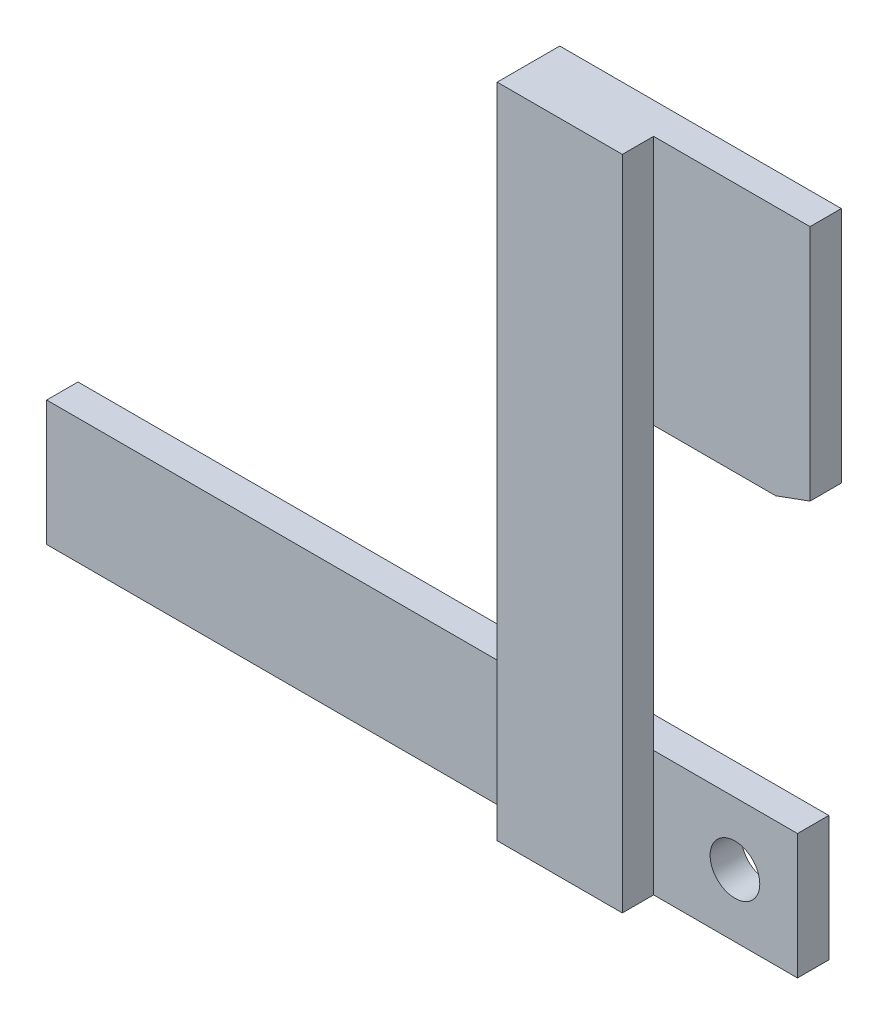
SolidWorks part; units mm, degrees
ref_plane "Front Plane" through (0, 0, 0) normal (0, 0, 1) x (1, 0, 0)
ref_plane "Top Plane" through (0, 0, 0) normal (0, 1, 0) x (1, 0, 0)
ref_plane "Right Plane" through (0, 0, 0) normal (1, 0, 0) x (0, 0, -1)
sketch "Sketch1" plane through (0, 0, 0) normal (0, 0, 1) x (1, 0, 0)
  line L1 (-76.2, -12.7) -> (76.2, -12.7)
  line L2 (-76.2, -12.7) -> (-76.2, 12.7)
  line L3 (-76.2, 12.7) -> (76.2, 12.7)
  line L4 (76.2, -12.7) -> (76.2, 12.7)
  line L5 (-76.2, -12.7) -> (76.2, 12.7) construction
  line L6 (-76.2, 12.7) -> (76.2, -12.7) construction
  point P0 (0, 0)
  dimension "D1" = 25.4
  dimension "D2" = 152.4
extrude "Extrude1" add sketch "Sketch1" along normal blind 6.35
sketch "Sketch2" plane through (0, 0, 6.35) normal (0, 0, 1) x (1, 0, 0)
  line L0 (-76.2, -12.7) -> (76.2, -12.7) construction
  line L1 (46.99, -12.7) -> (21.59, -12.7)
  line L2 (46.99, -12.7) -> (46.99, 120.65)
  line L3 (46.99, 120.65) -> (21.59, 120.65)
  line L4 (21.59, -12.7) -> (21.59, 120.65)
  line L5 (76.2, -12.7) -> (76.2, 12.7) construction
  dimension "D1" = 25.4
  dimension "D2" = 133.35
  dimension "D3" = 29.21
extrude "Extrude2" add sketch "Sketch2" along normal blind 6.35
sketch "Sketch3" plane through (0, 0, 6.35) normal (0, 0, -1) x (-1, 0, 0)
  line L0 (-46.99, 120.65) -> (-21.59, 120.65) construction
  line L1 (-21.59, 120.65) -> (-78.74, 120.65)
  line L2 (-21.59, 120.65) -> (-21.59, 69.85)
  line L3 (-21.59, 69.85) -> (-78.74, 69.85)
  line L4 (-78.74, 120.65) -> (-78.74, 69.85)
  line L6 (-21.59, 120.65) -> (-21.59, 12.7) construction
  dimension "D1" = 50.8
  dimension "D2" = 57.15
extrude "Extrude3" add sketch "Sketch3" along normal blind 6.35
chamfer "Chamfer1" distance 2.54 angle 70 1 edges at (78.74, 69.85, 3.175) first distance on face at (78.74, 95.25, 3.175)
sketch "Sketch4" plane through (0, 0, 6.35) normal (0, 0, 1) x (1, 0, 0)
  line L0 (76.2, 0) -> (63.5, 0) construction
  line L1 (76.2, -12.7) -> (76.2, 12.7) construction
  dimension "D1" = 12.7
hole_wizard "3/8 Clearance Hole1" positions "3DSketch1" profile "Sketch5" hole size "3/8" standard "Ansi Inch"
sketch3d "3DSketch1"
  point P0 (63.5, 0, 6.35)
sketch "Sketch5" plane through (63.5, 0, 6.35) normal (1, 0, 0) x (0, -1, 0)
  line L0 (0, 0) -> (0, 41.1295)
  line L1 (0, 41.1295) -> (5.0419, 38.1)
  line L2 (5.0419, 38.1) -> (5.0419, 0)
  line L5 (5.0419, 0) -> (0, 0)
  line L10 (0, 41.1295) -> (-5.0419, 38.1) construction
  line L11 (0, -6.35) -> (0, 107.95) construction
  dimension "Hole Dia." = 10.0838
  dimension "Hole Depth" = 38.1
  dimension "Drill Angle" = 118
